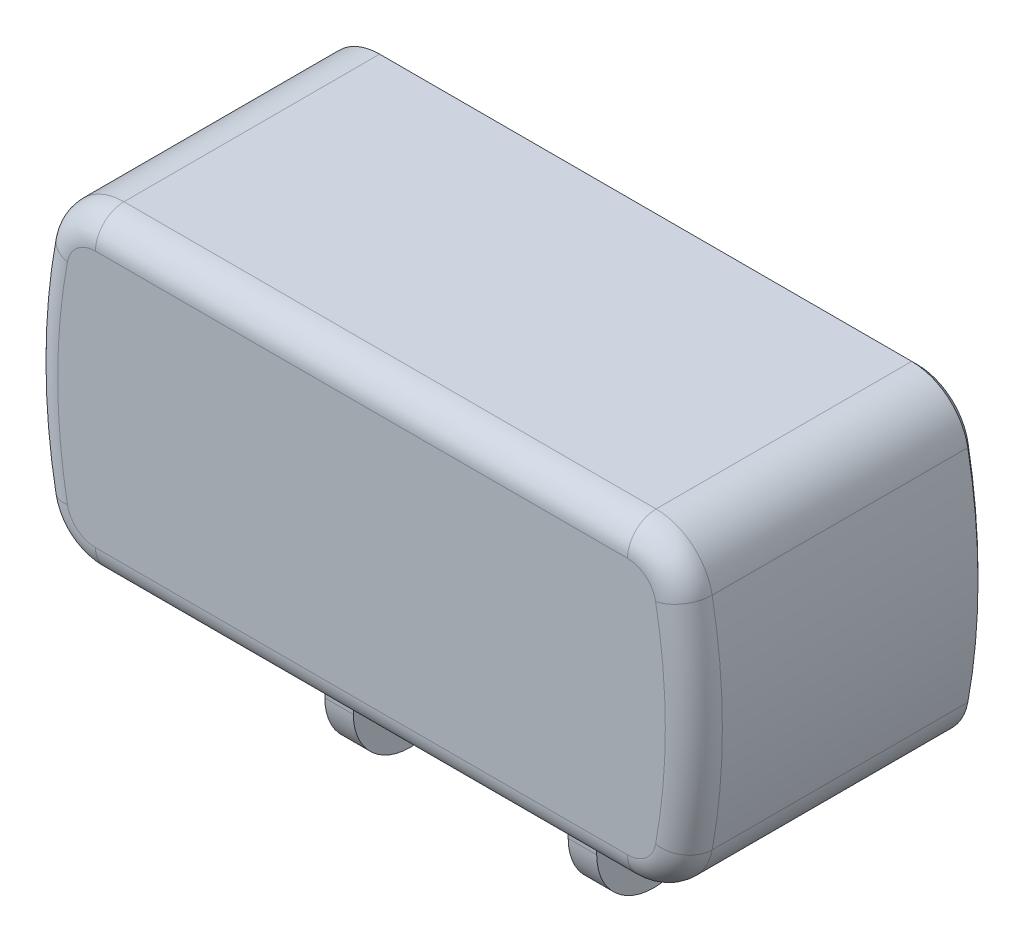
SolidWorks part; units mm, degrees
material "PLA"
ref_plane "Front Plane" through (0, 0, 0) normal (0, 0, 1) x (1, 0, 0)
ref_plane "Top Plane" through (0, 0, 0) normal (0, 1, 0) x (1, 0, 0)
ref_plane "Right Plane" through (0, 0, 0) normal (1, 0, 0) x (0, 0, -1)
sketch "Sketch2" plane through (0, 0, 0) normal (0, 0, 1) x (1, 0, 0)
  line L0 (-47.5, 0) -> (47.5, 0) construction
  line L1 (0, -27.5) -> (0, 27.5) construction
  line L2 (46.625, 27.5) -> (-46.625, 27.5)
  line L3 (46.625, -27.5) -> (-46.625, -27.5)
  arc A0 (-56.4565, 19.3279) -> (-56.4565, -19.3279) centre (47.5, 0) ccw
  arc A1 (-46.625, -27.5) -> (-56.4565, -19.3279) centre (-46.625, -17.5) cw
  arc A2 (-46.625, 27.5) -> (-56.4565, 19.3279) centre (-46.625, 17.5) ccw
  arc A3 (46.625, -27.5) -> (56.4565, -19.3279) centre (46.625, -17.5) ccw
  arc A4 (56.4565, 19.3279) -> (56.4565, -19.3279) centre (-47.5, 0) cw
  arc A5 (46.625, 27.5) -> (56.4565, 19.3279) centre (46.625, 17.5) cw
  point P4 (0, 0)
  point P8 (0, 0)
  dimension "D3" = 0
  dimension "D4" = 10
  dimension "D1" = 95
  dimension "D2" = 55
  dimension "D5" = 46.625
extrude "Boss-Extrude5" add sketch "Sketch2" along normal blind 50.8
fillet "Fillet9" radius 5 8 edges at (-58.238, 0, 50.8) (-53.0172, 25.1902, 50.8) (0, 27.5, 50.8) (53.0172, 25.1902, 50.8) (58.238, 0, 50.8) (53.0172, -25.1902, 50.8) (0, -27.5, 50.8) (-53.0172, -25.1902, 50.8)
sketch "Sketch3" plane through (0, 0, 0) normal (0, 0, -1) x (-1, 0, 0)
  line L0 (-55.738, 0) -> (55.738, 0) construction
  line L1 (0, 0) -> (0, 21.6868) construction
ref_plane "Plane1" through (-18.67, 0, 0) normal (1, 0, 0) x (0, 0, -1)
chamfer "Chamfer1" distance 1 angle 45 8 edges at (0, -27.5, 0) (53.0172, -25.1902, 0) (-53.0172, -25.1902, 0) (58.238, 0, 0) (53.0172, 25.1902, 0) (-53.0172, 25.1902, 0) (0, 27.5, 0) (-58.238, 0, 0)
sketch "Sketch8" plane through (18.825, 0, 0) normal (1, 0, 0) x (0, 0, -1)
  line L2 (-1, -27.5) -> (-45.8, -27.5)
  line L3 (-33.4051, -42.61) -> (-33.4051, -32.61)
  line L4 (-33.4137, -27.5) -> (-38.4137, -27.5)
  line L5 (-38.4137, -27.5) -> (-33.4051, -32.61)
  line L6 (-13.4051, -42.61) -> (-13.4051, -32.61)
  line L7 (-13.4051, -27.5) -> (-8.4051, -27.5)
  line L8 (-8.4051, -27.5) -> (-13.4051, -32.61)
  arc A0 (-33.4051, -42.61) -> (-13.4051, -42.61) centre (-23.4051, -42.61) ccw construction
  arc A2 (-33.4051, -42.61) -> (-13.4051, -42.61) centre (-23.4051, -42.61) ccw
  circle A4 centre (-23.4051, -35.61) radius 1.35
  circle A5 centre (-16.4051, -42.61) radius 1.35
  circle A6 centre (-23.4051, -49.61) radius 1.35
  circle A7 centre (-30.4051, -42.61) radius 1.35
  arc M14 (-25.0051, -42.61) -> (-21.8051, -42.61) centre (-23.4051, -42.61) cw
  arc M15 (-21.8051, -42.61) -> (-25.0051, -42.61) centre (-23.4051, -42.61) cw
  arc M16 (-13.7051, -42.61) -> (-33.1051, -42.61) centre (-23.4051, -42.61) ccw
  arc M17 (-33.1051, -42.61) -> (-13.7051, -42.61) centre (-23.4051, -42.61) ccw
  dimension "D1" = 2.7
  dimension "D2" = 10
  dimension "D3" = 5
  dimension "D4" = 5
extrude "Boss-Extrude6" add sketch "Sketch8" along normal blind 5 contours A2 L2 M16 M17 | A7 A6 A5 A4 M17 M16 M15 M14 region at (18.825, -32.2576, 23.4066) region at (18.825, -52.0356, 23.4051)
mirror "Mirror1" about plane through (0, 0, 0) normal (1, 0, 0) of "Boss-Extrude6"
sketch "Sketch4" plane through (0, 0, 0) normal (0, 0, -1) x (-1, 0, 0)
  line L1 (0, 27.5) -> (0, -27.5) construction
  line L3 (-46.625, 27.5) -> (46.625, 27.5) construction
  line L10 (46.625, -27.5) -> (-46.625, -27.5) construction
  line L11 (-58.238, 0) -> (58.238, 0) construction
  line L13 (-40.665, 14.165) -> (40.665, 14.165)
  line L14 (-45.665, 9.165) -> (-45.665, -9.165)
  line L15 (-40.665, -14.165) -> (40.665, -14.165)
  line L16 (45.665, 9.165) -> (45.665, -9.165)
  arc A0 (-56.4565, 19.3279) -> (-56.4565, -19.3279) centre (47.5, 0) ccw construction
  arc A1 (56.4565, -19.3279) -> (56.4565, 19.3279) centre (-47.5, 0) ccw construction
  arc A2 (40.665, -14.165) -> (45.665, -9.165) centre (40.665, -9.165) ccw
  arc A3 (-45.665, -9.165) -> (-40.665, -14.165) centre (-40.665, -9.165) ccw
  arc A4 (-40.665, 14.165) -> (-45.665, 9.165) centre (-40.665, 9.165) ccw
  arc A5 (40.665, 14.165) -> (45.665, 9.165) centre (40.665, 9.165) cw
  point P18 (0, 14.165)
  point P19 (-45.665, 0)
  point P24 (-45.665, -14.165)
  point P27 (-45.665, 14.165)
  point P30 (45.665, 14.165)
  dimension "D3" = 5
  dimension "D1" = 28.33
  dimension "D2" = 91.33
extrude "Cut-Extrude3" cut sketch "Sketch4" against normal blind 20
chamfer "Chamfer2" distance 20 angle 2 8 edges at (-45.665, 0, 20) (-44.2005, 12.7005, 20) (-44.2005, -12.7005, 20) (0, 14.165, 20) (0, -14.165, 20) (44.2005, 12.7005, 20) (44.2005, -12.7005, 20) (45.665, 0, 20) first distance on face at (-45.665, 0, 10) first distance on face at (-43.6828, 12.1828, 10) first distance on face at (-43.6828, -12.1828, 10) first distance on face at (0, 14.165, 10) first distance on face at (0, -14.165, 10) first distance on face at (43.6828, 12.1828, 10) first distance on face at (43.6828, -12.1828, 10) first distance on face at (45.665, 0, 10)
sketch "Sketch15" plane through (0, 0, 0) normal (0, 0, -1) x (-1, 0, 0)
  circle A0 centre (-48.2893, 18.5609) radius 1.35
  circle A2 centre (48.2893, -18.5609) radius 1.35
  circle A3 centre (48.2893, 18.5609) radius 1.35
  circle A4 centre (-48.2893, -18.5609) radius 1.35
  dimension "D1" = 2.7
extrude "Cut-Extrude4" cut sketch "Sketch15" against normal blind 5
